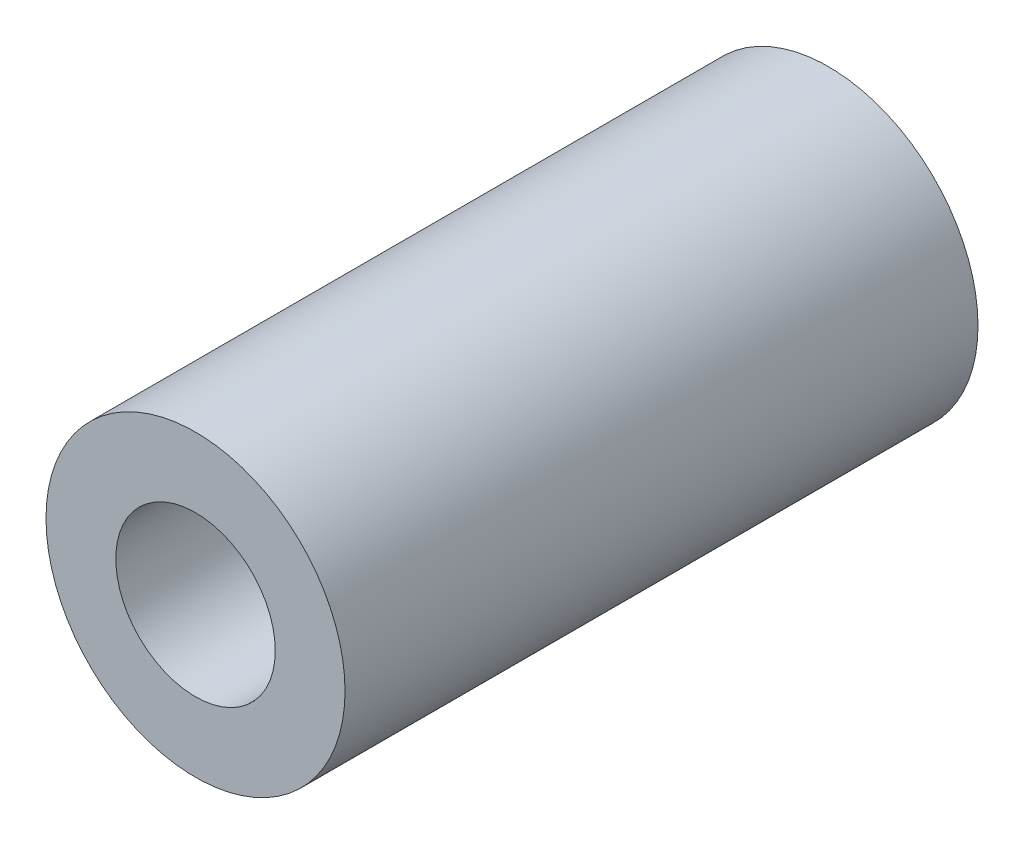
SolidWorks part; units mm, degrees
ref_plane "Front Plane" through (0, 0, 0) normal (0, 0, 1) x (1, 0, 0)
ref_plane "Top Plane" through (0, 0, 0) normal (0, 1, 0) x (1, 0, 0)
ref_plane "Right Plane" through (0, 0, 0) normal (1, 0, 0) x (0, 0, -1)
sketch "Sketch1" plane through (0, 0, 0) normal (0, 0, 1) x (1, 0, 0)
  circle A0 centre (0, 0) radius 3
  circle A1 centre (0, 0) radius 1.6
  dimension "OD" = 6
  dimension "ID" = 3.2
extrude "Extrude1" add sketch "Sketch1" along normal mid plane 12.7
sketch "Sketch2" plane through (0, 0, 0) normal (1, 0, 0) x (0, 0, -1)
  line L0 (-6.35, -1.6) -> (6.35, -1.6) construction
  line L3 (6.35, 1.6) -> (-6.35, 1.6) construction
  line L5 (-6.35, -1.6) -> (6.35, -1.6)
  line L6 (6.35, 1.6) -> (-6.35, 1.6)
sketch "Sketch4" plane through (0, 0, 6.35) normal (0, 0, 1) x (1, 0, 0)
  line L0 (0, 0) -> (-1.1314, 1.1314)
  line L1 (0, -3.3) -> (0, 3.3) construction
  circle A0 centre (0, 0) radius 1.6 construction
  dimension "D1" = 45
